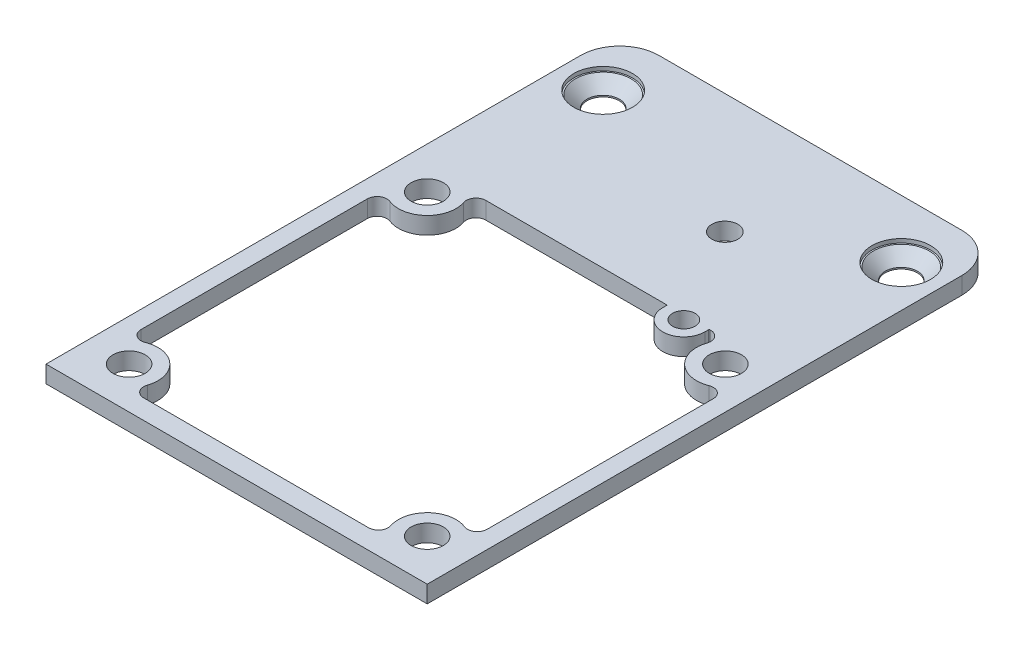
SolidWorks part; units mm, degrees
ref_plane "Front Plane" through (0, 0, 0) normal (0, 0, 1) x (1, 0, 0)
ref_plane "Top Plane" through (0, 0, 0) normal (0, 1, 0) x (1, 0, 0)
ref_plane "Right Plane" through (0, 0, 0) normal (1, 0, 0) x (0, 0, -1)
sketch "Sketch1" plane through (0, 0, 0) normal (0, 1, 0) x (1, 0, 0)
  line L0 (-15.5, 39.2) -> (15.5, 39.2)
  line L1 (-18.2, 15) -> (-18.2, -15) construction
  line L2 (17.7, -17.4996) -> (-17.7, -17.4996)
  line L3 (17.7, -17.4996) -> (17.7, 17.4996)
  line L4 (17.7, 17.4996) -> (-17.7, 17.4996)
  line L5 (-17.7, -17.4996) -> (-17.7, 17.4996)
  line L6 (17.7, -17.4996) -> (-17.7, 17.4996) construction
  line L7 (-19.5, 35.2) -> (-19.5, -19.5)
  line L8 (-19.5, -19.5) -> (19.5, -19.5)
  line L9 (19.5, -19.5) -> (19.5, 35.2)
  line L10 (17.7, 17.4996) -> (-17.7, -17.4996) construction
  line L11 (-15.25, 15.25) -> (-15.25, 17.9996) construction
  line L12 (11.35, 17.05) -> (11.35, 17.4996)
  line L13 (7.05, 17.05) -> (7.05, 17.4996)
  arc A0 (19.5, 35.2) -> (15.5, 39.2) centre (15.5, 35.2) ccw construction
  arc A1 (-15.5, 39.2) -> (-19.5, 35.2) centre (-15.5, 35.2) ccw construction
  arc A2 (19.5, 35.2) -> (15.5, 39.2) centre (15.5, 35.2) ccw
  arc A3 (-15.5, 39.2) -> (-19.5, 35.2) centre (-15.5, 35.2) ccw
  circle A4 centre (-15.25, -15.25) radius 1.65 construction
  circle A5 centre (15.25, -15.25) radius 1.65 construction
  circle A6 centre (-15.25, 15.25) radius 1.65 construction
  circle A7 centre (15.25, 15.25) radius 1.65 construction
  circle A8 centre (-15.25, 33.25) radius 1.65 construction
  circle A9 centre (15.25, 33.25) radius 1.65 construction
  circle A10 centre (-15.25, -15.25) radius 1.65
  circle A11 centre (15.25, -15.25) radius 1.65
  circle A12 centre (-15.25, 15.25) radius 1.65
  circle A13 centre (15.25, 15.25) radius 1.65
  circle A14 centre (-15.25, 33.25) radius 1.65
  circle A15 centre (15.25, 33.25) radius 1.65
  arc A16 (-15.2, 18) -> (-18.2, 15) centre (-15.2, 15) ccw construction
  circle A17 centre (-15.25, 15.25) radius 2.95
  circle A18 centre (15.25, 15.25) radius 2.95
  circle A19 centre (-15.25, -15.25) radius 2.95
  circle A20 centre (15.25, -15.25) radius 2.95
  circle A21 centre (3.5, 26.95) radius 1.33 construction
  circle A22 centre (9.2, 17.05) radius 2.15
  circle A23 centre (9.2, 17.05) radius 1.15
  circle A24 centre (9.2, 17.05) radius 0.9 construction
  circle A25 centre (3.5, 26.95) radius 1.33
  point P29 (0, 0)
  dimension "D3" = 2.3
  dimension "D4" = 1
  dimension "D1" = 0.5
  dimension "D2" = 0.5
extrude "Base shape" add sketch "Sketch1" along normal blind 1.75 contours L0 A3 L7 L8 L9 A2 A20 L3 L2 A19 L5 A17 L4 A18 A15 A14 | A17 L4 L5 | L4 A17 L5 A12 | L5 A17 | L4 A17 | L3 A18 L4 A13 | L3 A18 | L4 A18 | L2 A19 L5 A10 | L2 A19 | L5 A19 | A19 L5 L2 | L2 A20 L3 A11 | L3 A20 | L2 A20 | A20 L2 L3 | A18 L3 L4 | A23 L4 A22 | A23 L4 A22 | A22 L4 L13 | A22 L12 L4 region at (-0.0683, 0, -21.3921) region at (17.5279, 0, 17.307) region at (15.25, 0, 17.7828) region at (15.25, 0, 17.4246) region at (17.9015, 0, 15.25) region at (-15.25, 0, 17.7828) region at (-15.25, 0, 17.4246) region at (13.3348, 0, -13.1057) region at (17.9015, 0, -15.25) region at (-17.5279, 0, 17.307) region at (17.5279, 0, -17.307) region at (15.25, 0, -17.7828) region at (-17.9015, 0, 15.25) region at (11.3358, 0, -17.3874) region at (-17.9015, 0, -15.25) region at (-17.625, 0, -15.25) region at (11.2881, 0, -17.2708) region at (9.2, 0, -18.3154) region at (-17.5279, 0, -17.307) region at (7.0642, 0, -17.3874) region at (-15.25, 0, -17.7828)
fillet "Milling fillets" radius 1 8 edges at (-17.7, 0.875, 13.6068) (-13.3416, 0.875, 17.4996) (13.3416, 0.875, 17.4996) (17.7, 0.875, 13.6068) (17.7, 0.875, -13.6068) (13.3416, 0.875, -17.4996) (-13.3416, 0.875, -17.4996) (-17.7, 0.875, -13.6068)
sketch "Sketch3" plane through (0, 1.75, 0) normal (0, 1, 0) x (1, 0, 0)
  circle A0 centre (-15.25, 33.25) radius 3
  circle A1 centre (15.25, 33.25) radius 3
  dimension "D1" = 6
extrude "Screw head cut" cut sketch "Sketch3" against normal blind 0.4
chamfer "Screw head chamfer" distance 1.2 angle 45 2 edges at (15.25, 1.35, -31.6) (-15.25, 1.35, -31.6)
